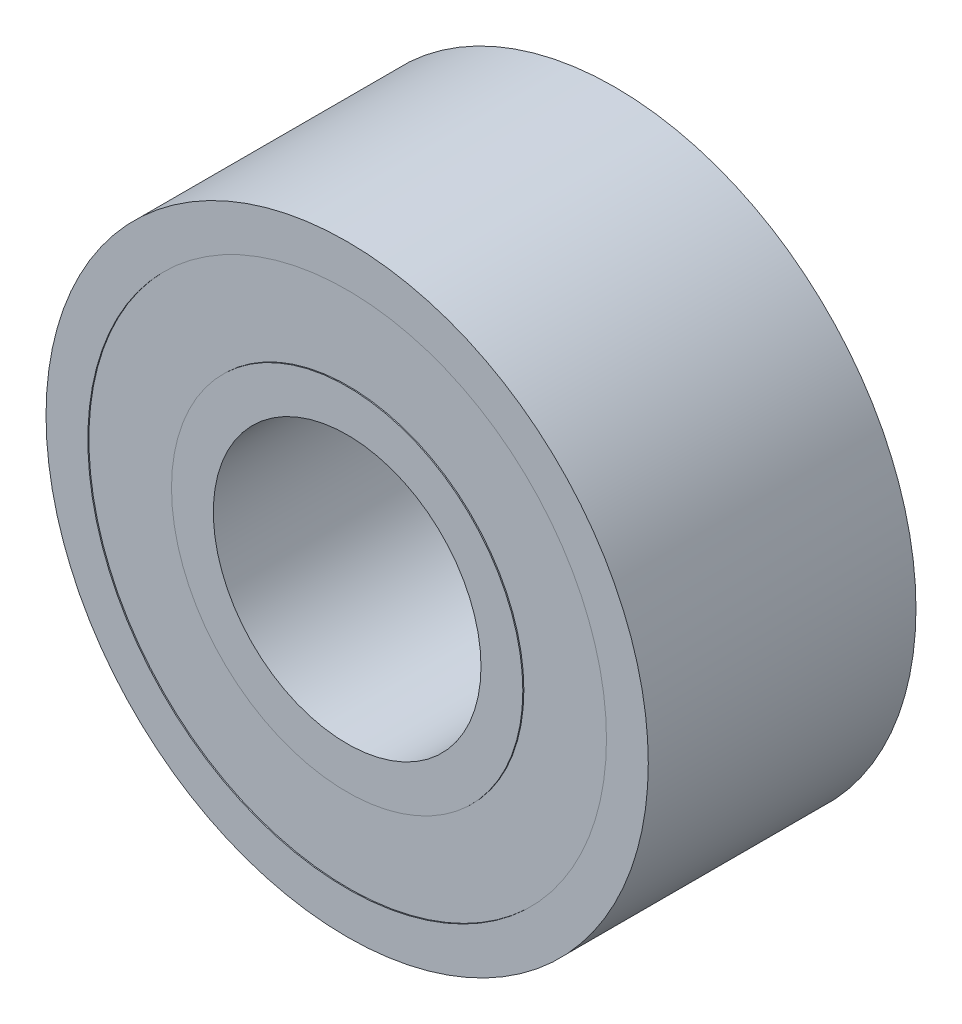
SolidWorks part; units mm, degrees
material "Chrome Stainless Steel"
ref_plane "Front Plane" through (0, 0, 0) normal (0, 0, 1) x (1, 0, 0)
ref_plane "Top Plane" through (0, 0, 0) normal (0, 1, 0) x (1, 0, 0)
ref_plane "Right Plane" through (0, 0, 0) normal (1, 0, 0) x (0, 0, -1)
sketch "Sketch1" plane through (0, 0, 0) normal (0, 0, 1) x (1, 0, 0)
  circle A0 centre (0, 0) radius 2
  circle A1 centre (0, 0) radius 2.625
  circle A2 centre (0, 0) radius 4.5
  circle A3 centre (0, 0) radius 3.875
  dimension "D1" = 9
  dimension "D2" = 4
  dimension "D3" = 5.25
  dimension "D4" = 7.75
extrude "Boss-Extrude1" add sketch "Sketch1" along normal blind 2 and the other way blind 2 contours A2 A3 | A1 A0 region at (-2.5508, 0, 0) region at (-4.3727, 0, 0)
extrude "Boss-Extrude2" add sketch "Sketch1<3>" along normal blind 1.9844 and the other way blind 1.9844 contours A3 A1 region at (-3.7654, 0, 0)
sketch "Sketch1<3>" plane through (0, 0, 0) normal (0, 0, 1) x (1, 0, 0) same geometry as "Sketch1"
equation "\"D1@Boss-Extrude2\"=2mm-1/64"
equation "\"D2@Boss-Extrude2\"=2mm-1/64"
